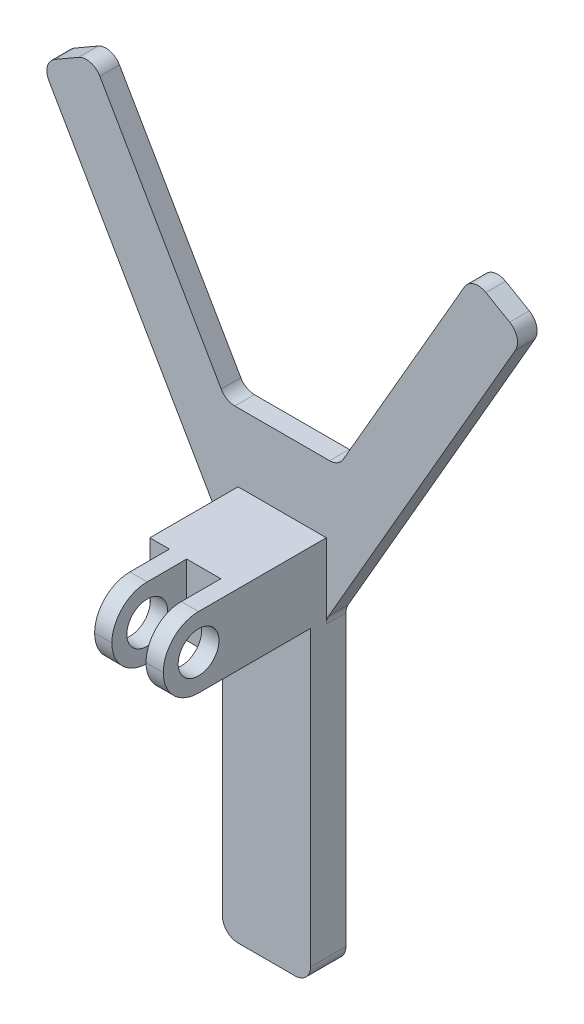
SolidWorks part; units mm, degrees
ref_plane "Plan de face" through (0, 0, 0) normal (0, 0, 1) x (1, 0, 0)
ref_plane "Plan de dessus" through (0, 0, 0) normal (0, 1, 0) x (1, 0, 0)
ref_plane "Plan de droite" through (0, 0, 0) normal (1, 0, 0) x (0, 0, -1)
sketch "Sketch1" plane through (0, 0, 0) normal (0, 0, 1) x (1, 0, 0)
  line L18 (-18.2712, 45) -> (18.2712, 45)
  line L19 (18.2712, 45) -> (61.5725, 120)
  line L20 (61.5725, 120) -> (78.0703, 110.475)
  line L21 (78.0703, 110.475) -> (14.2875, 0)
  line L23 (14.2875, 0) -> (14.2875, -100)
  line L24 (14.2875, -100) -> (-14.2875, -100)
  line L25 (-14.2875, -100) -> (-14.2875, 0)
  line L26 (-14.2875, 0) -> (-78.0703, 110.475)
  line L27 (-78.0703, 110.475) -> (-61.5725, 120)
  line L28 (-61.5725, 120) -> (-18.2712, 45)
  line L29 (-14.2875, 0) -> (14.2875, 0) construction
  point P2 (0, 0)
  point P12 (0, 45)
  dimension "D1" = 28.575
  dimension "D2" = 19.05
  dimension "D3" = 45
  dimension "D4" = 60
  dimension "D5" = 100
  dimension "D6" = 120
extrude "Boss-Extrude1" add sketch "Sketch1" along normal blind 6.35
sketch "Sketch3" plane through (0, 0, 6.35) normal (0, 0, 1) x (1, 0, 0)
  line L0 (0, 45) -> (0, 0) construction
  line L5 (14.2875, 0) -> (-14.2875, 0)
  line L6 (14.2875, 0) -> (14.2875, 22.86)
  line L7 (14.2875, 22.86) -> (-14.2875, 22.86)
  line L8 (-14.2875, 0) -> (-14.2875, 22.86)
  line L9 (14.2875, 0) -> (-14.2875, 22.86) construction
  line L10 (14.2875, 22.86) -> (-14.2875, 0) construction
  line L12 (18.2712, 45) -> (-18.2712, 45) construction
  point P0 (0, 30)
  point P8 (0, 0)
  dimension "D1" = 28.575
  dimension "D2" = 22.86
extrude "Boss-Extrude2" add sketch "Sketch3" along normal blind 52.8
sketch "Sketch6" plane through (0, 0, 6.35) normal (0, 0, 1) x (1, 0, 0)
  line L6 (-14.2875, 0) -> (-14.2875, -100) construction
  line L11 (-14.2875, 0) -> (14.2875, 0)
  line L12 (-14.2875, 0) -> (-14.2875, -100)
  line L13 (-14.2875, -100) -> (14.2875, -100)
  line L14 (14.2875, 0) -> (14.2875, -100)
  line L15 (-14.2875, -100) -> (14.2875, -100) construction
  line L16 (14.2875, -100) -> (14.2875, 0) construction
  line L17 (-14.2875, 0) -> (14.2875, 0) construction
extrude "Boss-Extrude3" add sketch "Sketch6" along normal blind 5.08
fillet "Fillet1" radius 5.08 10 edges at (-14.2875, -100, 5.715) (14.2875, -100, 5.715) (78.0703, 110.475, 3.175) (61.5725, 120, 3.175) (-61.5725, 120, 3.175) (-78.0703, 110.475, 3.175) (-18.2712, 45, 3.175) (18.2712, 45, 3.175) (14.2875, 0, 3.175) (-14.2875, 0, 3.175)
sketch "Sketch4" plane through (0, 0, 0) normal (0, -1, 0) x (1, 0, 0)
  line L0 (-14.2875, 59.15) -> (14.2875, 59.15) construction
  line L1 (-14.2875, 59.15) -> (-7.9375, 59.15)
  line L2 (-14.2875, 59.15) -> (-14.2875, 34.925)
  line L3 (-14.2875, 34.925) -> (-7.9375, 34.925)
  line L4 (-7.9375, 59.15) -> (-7.9375, 34.925)
  line L5 (-2.3495, 59.15) -> (8.6995, 59.15)
  line L6 (-2.3495, 59.15) -> (-2.3495, 34.925)
  line L7 (-2.3495, 34.925) -> (8.6995, 34.925)
  line L8 (8.6995, 59.15) -> (8.6995, 34.925)
  line L9 (14.2875, 59.15) -> (14.2875, 11.43) construction
  dimension "D1" = 5.588
  dimension "D2" = 5.588
  dimension "D3" = 24.225
  dimension "D4" = 24.225
  dimension "D5" = 6.35
extrude "Cut-Extrude1" cut sketch "Sketch4" against normal through all
fillet "Fillet3" radius 11.43 4 edges at (11.4935, 22.86, 59.15) (-5.1435, 22.86, 59.15) (11.4935, 0, 59.15) (-5.1435, 0, 59.15)
sketch "Sketch5" plane through (-7.9375, 0, 0) normal (-1, 0, 0) x (0, 0, 1)
  circle A0 centre (47.72, 11.43) radius 6.604
  dimension "D1" = 13.208
extrude "Cut-Extrude2" cut sketch "Sketch5" against normal through all
